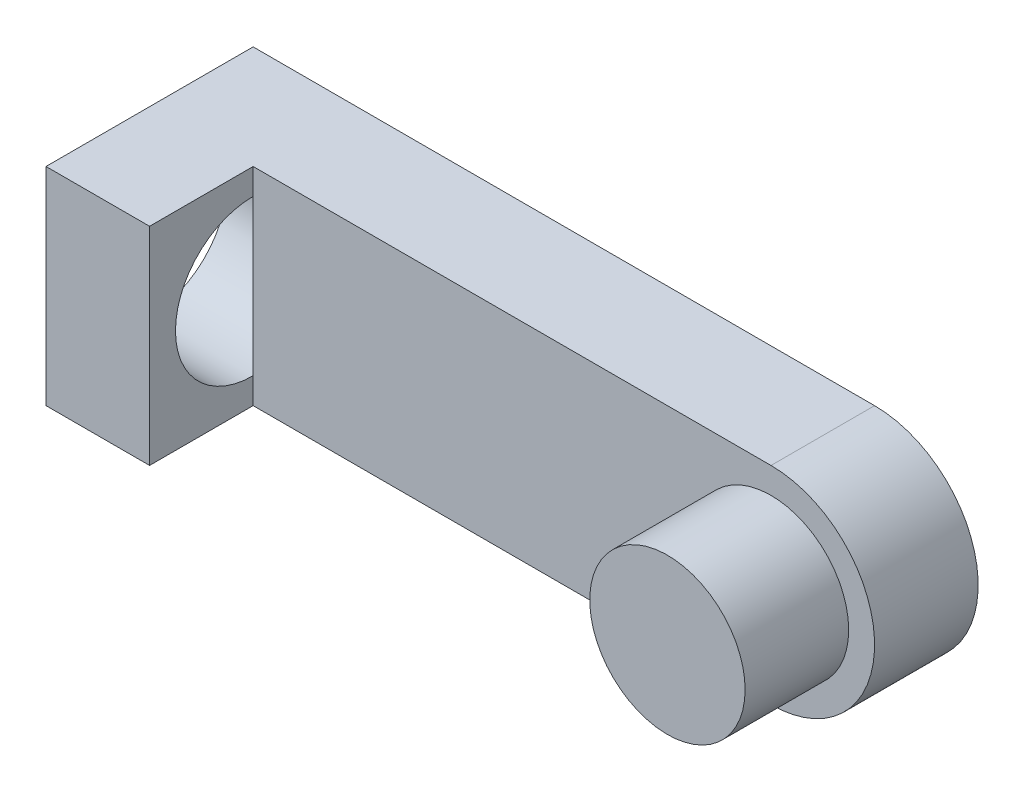
SolidWorks part; units mm, degrees
ref_plane "Front Plane" through (0, 0, 0) normal (0, 0, 1) x (1, 0, 0)
ref_plane "Top Plane" through (0, 0, 0) normal (0, 1, 0) x (1, 0, 0)
ref_plane "Right Plane" through (0, 0, 0) normal (1, 0, 0) x (0, 0, -1)
sketch "Sketch1" plane through (0, 0, 0) normal (0, 0, 1) x (1, 0, 0)
  line L1 (-76.2, -25.4) -> (76.2, -25.4)
  line L2 (-76.2, -25.4) -> (-76.2, 25.4)
  line L3 (-76.2, 25.4) -> (76.2, 25.4)
  line L4 (76.2, -25.4) -> (76.2, 25.4)
  line L5 (-76.2, -25.4) -> (76.2, 25.4) construction
  line L6 (-76.2, 25.4) -> (76.2, -25.4) construction
  circle A1 centre (76.2, 0) radius 25.4
  point P0 (0, 0)
  dimension "D1" = 50.8
  dimension "D2" = 152.4
extrude "Boss-Extrude1" add sketch "Sketch1" along normal blind 25.4 contours L2 L1 L4 L3 | A1
sketch "Sketch3" plane through (0, 0, 25.4) normal (0, 0, 1) x (1, 0, 0)
  circle A0 centre (76.2, 0) radius 19.05
  arc A2 (76.2, -25.4) -> (76.2, 25.4) centre (76.2, 0) ccw construction
  dimension "D1" = 38.1
extrude "Boss-Extrude2" add sketch "Sketch3" along normal blind 25.4
sketch "Sketch4" plane through (0, 0, 25.4) normal (0, 0, 1) x (1, 0, 0)
  line L0 (-76.2, -25.4) -> (76.2, -25.4) construction
  line L1 (-76.2, 25.4) -> (-50.8, 25.4)
  line L2 (-76.2, 25.4) -> (-76.2, -25.4)
  line L3 (-76.2, -25.4) -> (-50.8, -25.4)
  line L4 (-50.8, 25.4) -> (-50.8, -25.4)
  dimension "D1" = 25.4
extrude "Boss-Extrude3" add sketch "Sketch4" along normal blind 25.4
sketch "Sketch5" plane through (-76.2, 0, 0) normal (-1, 0, 0) x (0, 0, 1)
  line L0 (0, 0) -> (50.8, 0) construction
  line L1 (0, -25.4) -> (0, 25.4) construction
  line L2 (50.8, 25.4) -> (50.8, -25.4) construction
  line L3 (25.4, 25.4) -> (25.4, -25.4) construction
  line L4 (50.8, 25.4) -> (0, 25.4) construction
  circle A0 centre (25.4, 0) radius 19.05
  point P13 (25.4, 0)
  dimension "D1" = 38.1
extrude "Cut-Extrude1" cut sketch "Sketch5" against normal blind 25.4 contours A0
